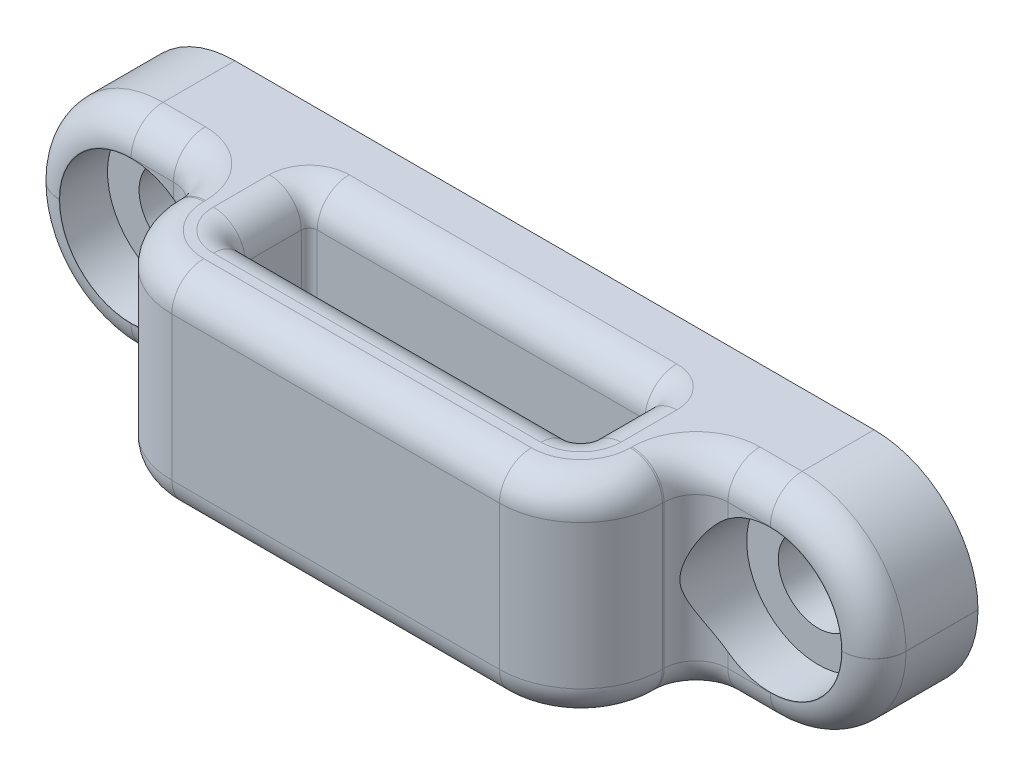
SolidWorks part; units mm, degrees
ref_plane "xy_plane" through (0, 0, 0) normal (0, 0, 1) x (1, 0, 0)
ref_plane "zx_plane" through (0, 0, 0) normal (0, 1, 0) x (1, 0, 0)
ref_plane "yz_plane" through (0, 0, 0) normal (1, 0, 0) x (0, 0, -1)
ref_axis "x_axis" through (-80.9, 0, 0) along (1, 0, 0)
ref_axis "y_axis" through (0, -50, 0) along (0, 1, 0)
ref_axis "z_axis" through (0, 0, -80.9) along (0, 0, 1)
ref_plane "yMid_plane" through (0, 0, 0) normal (0, 1, 0) x (1, 0, 0)
ref_plane "yMax_plane" through (0, 6.505, 0) normal (0, 1, 0) x (1, 0, 0)
ref_plane "yMin_plane" through (0, -6.505, 0) normal (0, 1, 0) x (1, 0, 0)
ref_plane "xMid_plane" through (0, 0, 0) normal (1, 0, 0) x (0, 0, -1)
ref_plane "xMax_plane" through (26.5, 0, 0) normal (1, 0, 0) x (0, 0, -1)
ref_plane "xMin_plane" through (-26.5, 0, 0) normal (1, 0, 0) x (0, 0, -1)
ref_plane "clampHoleTop_plane" through (0, 0, 3.5) normal (0, 0, 1) x (1, 0, 0)
ref_plane "screwHeadTopClearance_plane" through (0, 0, 6.5) normal (0, 0, 1) x (1, 0, 0)
sketch "strapSlot_sketch" plane through (0, 0, 0) normal (0, 1, 0) x (1, 0, 0)
  line L0 (-10.25, -9.1) -> (10.25, -9.1)
  line L1 (10.75, -8.6) -> (10.75, -5.1)
  line L2 (10.25, -4.6) -> (-10.25, -4.6)
  line L3 (-10.75, -5.1) -> (-10.75, -8.6)
  arc A0 (10.75, -5.1) -> (10.25, -4.6) centre (10.25, -5.1) ccw
  arc A1 (-10.25, -4.6) -> (-10.75, -5.1) centre (-10.25, -5.1) ccw
  arc A2 (-10.25, -9.1) -> (-10.75, -8.6) centre (-10.25, -8.6) cw
  arc A3 (10.25, -9.1) -> (10.75, -8.6) centre (10.25, -8.6) ccw
  point P3 (0, -4.6)
  point P8 (10.75, -4.6)
  point P11 (-10.75, -4.6)
  point P16 (10.75, -9.1)
  dimension "D2" = 0.5
  dimension "D3" = 21.5
  dimension "D4" = 4.5
  dimension "D1" = 4.6
sketch "strapSlotWalls_sketch" plane through (0, 0, 0) normal (0, 1, 0) x (1, 0, 0)
  line L14 (-10.25, -13.7) -> (10.25, -13.7)
  line L15 (-15.35, -5.1) -> (-15.35, -8.6)
  line L16 (10.25, 0) -> (-10.25, 0)
  line L17 (15.35, -8.6) -> (15.35, -5.1)
  line L18 (-10.25, -13.7) -> (10.25, -13.7)
  line L19 (-15.35, 0) -> (-15.35, -8.6)
  line L20 (15.35, 0) -> (-15.35, 0)
  line L21 (15.35, -8.6) -> (15.35, 0)
  arc A10 (-15.35, -8.6) -> (-10.25, -13.7) centre (-10.25, -8.6) ccw
  arc A11 (-10.25, 0) -> (-15.35, -5.1) centre (-10.25, -5.1) ccw
  arc A12 (15.35, -5.1) -> (10.25, 0) centre (10.25, -5.1) ccw
  arc A13 (10.25, -13.7) -> (15.35, -8.6) centre (10.25, -8.6) ccw
  arc A14 (-15.35, -8.6) -> (-10.25, -13.7) centre (-10.25, -8.6) ccw
  arc A17 (10.25, -13.7) -> (15.35, -8.6) centre (10.25, -8.6) ccw
  dimension "D1" = 4.6
sketch "mountHolePositions_sketch" plane through (0, 0, 0) normal (0, 0, 1) x (1, 0, 0)
  line L1 (-20, 0) -> (20, 0)
  line L2 (50, 0) -> (-50, 0) construction
  dimension "D1" = 40
sketch "mountingWings_sketch" plane through (0, 0, 0) normal (0, 0, 1) x (1, 0, 0)
  line L0 (55, -6.505) -> (-55, -6.505) construction
  line L1 (-20, -6.505) -> (20, -6.505)
  line L2 (-26.5, -0.005) -> (-26.5, 0.005)
  line L3 (-20, 6.505) -> (20, 6.505)
  line L4 (26.5, -0.005) -> (26.5, 0.005)
  line L5 (55, 6.505) -> (-55, 6.505) construction
  line L6 (-26.5, -55) -> (-26.5, 55) construction
  line L7 (26.5, -55) -> (26.5, 55) construction
  arc A0 (20, -6.505) -> (26.5, -0.005) centre (20, -0.005) ccw
  arc A1 (20, 6.505) -> (26.5, 0.005) centre (20, 0.005) cw
  arc A2 (-26.5, 0.005) -> (-20, 6.505) centre (-20, 0.005) cw
  arc A3 (-20, -6.505) -> (-26.5, -0.005) centre (-20, -0.005) cw
  dimension "D1" = 6.5
sketch "screwHeadClearanceHoles_sketch" plane through (0, 0, 0) normal (0, 0, 1) x (1, 0, 0)
  circle A0 centre (-20, 0) radius 4.475
  circle A1 centre (20, 0) radius 4.475
  dimension "D1" = 8.95
sketch "screwClearanceHoles_sketch" plane through (0, 0, 0) normal (0, 0, 1) x (1, 0, 0)
  circle A0 centre (-20, 0) radius 2.5
  circle A1 centre (20, 0) radius 2.5
  dimension "D1" = 5
extrude "strapSurroundingMeat_extrude" add sketch "strapSlotWalls_sketch" along normal up to surface (6.505 mm away) from surface up to plane "yMax_plane" starting at plane "yMin_plane"
extrude "mountingWings_extrude" add sketch "mountingWings_sketch" along normal blind 6.5 from surface starting at plane "xy_plane"
extrude "strapSlot_extrude" cut sketch "strapSlot_sketch" against normal through all both and the other way through all from surface starting at plane "yMid_plane"
fillet "slotBuglingFillet" radius 2 16 edges at (0, 6.505, 4.6) (-10.75, 6.505, 6.85) (0, 6.505, 9.1) (10.75, 6.505, 6.85) (-10.75, -6.505, 6.85) (0, -6.505, 4.6) (10.75, -6.505, 6.85) (0, -6.505, 9.1) (10.6036, 6.505, 4.7464) (-10.6036, 6.505, 4.7464) (-10.6036, 6.505, 8.9536) (10.6036, 6.505, 8.9536) (-10.6036, -6.505, 8.9536) (-10.6036, -6.505, 4.7464) (10.6036, -6.505, 4.7464) (10.6036, -6.505, 8.9536)
fillet "cosmeticFillet" radius 2 22 edges at (-15.35, -6.505, 7.55) (-13.8562, -6.505, 12.2062) (0, -6.505, 13.7) (13.8562, -6.505, 12.2062) (15.35, -6.505, 7.55) (-15.35, 6.505, 7.55) (-13.8562, 6.505, 12.2062) (0, 6.505, 13.7) (13.8562, 6.505, 12.2062) (15.35, 6.505, 7.55) (-17.675, -6.505, 6.5) (-24.5962, -4.6012, 6.5) (-26.5, 0, 6.5) (-24.5962, 4.6012, 6.5) (-17.675, 6.505, 6.5) (-15.35, 0, 6.5) (17.675, 6.505, 6.5) (24.5962, 4.6012, 6.5) (26.5, 0, 6.5) (24.5962, -4.6012, 6.5) (17.675, -6.505, 6.5) (15.35, 0, 6.5) tangent propagation no
extrude "screwClearanceHoles_cut" cut sketch "screwClearanceHoles_sketch" along normal through all
extrude "screwHeadClearanceHoles_cut" cut sketch "screwHeadClearanceHoles_sketch" along normal through all from surface starting at plane "clampHoleTop_plane"
equation "\"strapWidth\"= 20mm"
equation "\"strapThickness\"= 3.2mm"
equation "\"slotWidth\"= \"strapWidth\" + 2 * \"slotCornerRoundingFilletRadius\" + 2 * \"3dPrinterNoodleBulgeCompensation\""
equation "\"slotThickness\"= 4.5mm"
equation "\"D3@strapSlot_sketch\"=\"slotWidth\""
equation "\"D4@strapSlot_sketch\"=\"slotThickness\""
equation "\"extentY\"= 13.01mm"
equation "\"D1@yMax_plane\"=\"extentY\"/2"
equation "\"D1@yMin_plane\"=\"extentY\"/2"
equation "\"mountHolesIntervalX\"= ( fix ( \"minimumAllowedMountHolesIntervalX\" / \"mountHolesIntervalPreferredIncrement\" ) + iif ( fix ( \"minimumAllowedMountHolesIntervalX\" / \"mountHolesIntervalPreferredIncrement\" ) = ( \"minimumAllowedMountHolesIntervalX\" / \"mountHolesIntervalPreferredIncrement\" ) , 0 , 1 ) ) * \"mountHolesIntervalPreferredIncrement\""
equation "\"D1@mountHolePositions_sketch\"= \"mountHolesIntervalX\""
equation "\"D1@screwClearanceHoles_sketch\" = \"mountScrewClearanceDiameter\""
equation "\"D1@screwHeadClearanceHoles_sketch\" = \"mountScrewHeadClearanceDiameter\""
equation "\"strapSlotWallThickness\"= 4.6mm"
equation "\"D1@strapSlot_sketch\"=\"strapSlotWallThickness\""
equation "\"mountScrewClampingThickness\"= 3.5mm"
equation "\"mountScrewHeadClearanceThickness\"= 3mm"
equation "\"mountScrewClearanceDiameter\"= 4.50mm + 2 * \"3dPrinterNoodleBulgeCompensation\""
equation "\"mountScrewHeadClearanceDiameter\"= 8.45mm + 2 * \"3dPrinterNoodleBulgeCompensation\""
equation "\"mountScrewClampingDiameter\"= 13"
equation "\"D1@mountingWings_sketch\" = \"extentX\""
equation "\"extentX\"= \"mountHolesIntervalX\" + \"mountScrewClampingDiameter\""
equation "\"wingThickness\"= \"mountScrewClampingThickness\" + \"mountScrewHeadClearanceThickness\""
equation "\"D1@clampHoleTop_plane\"=\"mountScrewClampingThickness\""
equation "\"D1@screwHeadTopClearance_plane\"=\"mountScrewHeadClearanceThickness\""
equation "\"minimumAllowedMountHolesIntervalX\"= \"slotWidth\" + 2 * \"strapSlotWallThickness\" + \"mountScrewHeadClearanceDiameter\""
equation "\"mountHolesIntervalPreferredIncrement\"= 5mm"
equation "\"D1@strapSlotWalls_sketch\"=\"strapSlotWallThickness\""
equation "\"D2@strapSlot_sketch\" = \"slotCornerRoundingFilletRadius\""
equation "\"buglingFilletRadius\"= 2mm"
equation "\"D1@slotBuglingFillet\" = \"buglingFilletRadius\""
equation "\"slotCornerRoundingFilletRadius\"= 0.5mm"
equation "\"cosmeticFilletRadius\"= 2mm"
equation "\"D1@xMax_plane\"=\"extentX\"/2"
equation "\"D1@xMin_plane\"=\"extentX\"/2"
equation "\"D1@mountingWings_sketch\" = \"mountScrewClampingDiameter\" / 2"
equation "\"D1@mountingWings_extrude\" = \"wingThickness\""
equation "\"D1@cosmeticFillet\"=\"cosmeticFilletRadius\""
equation "\"3dPrinterNoodleBulgeCompensation\"= 0.25mm"
